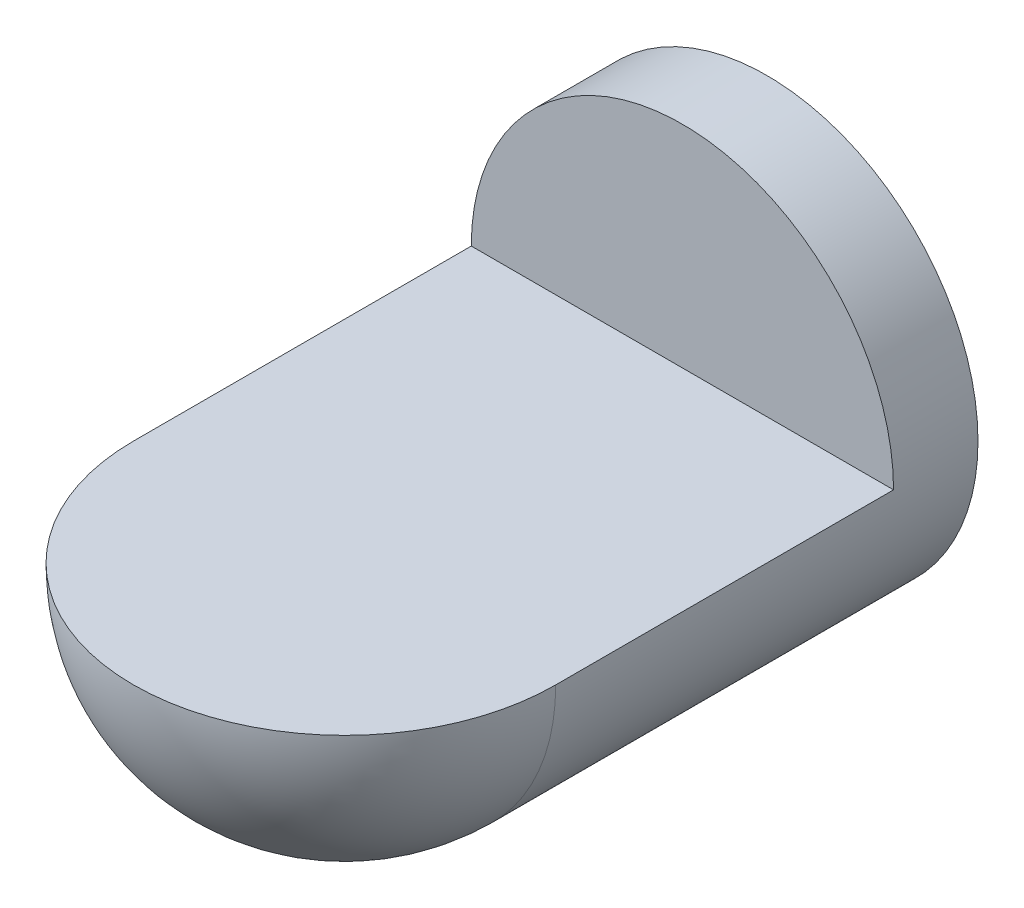
SolidWorks part; units mm, degrees
ref_plane "Front Plane" through (0, 0, 0) normal (0, 0, 1) x (1, 0, 0)
ref_plane "Top Plane" through (0, 0, 0) normal (0, 1, 0) x (1, 0, 0)
ref_plane "Right Plane" through (0, 0, 0) normal (1, 0, 0) x (0, 0, -1)
sketch "Sketch1" plane through (0, 0, 0) normal (1, 0, 0) x (0, 0, -1)
  line L0 (-146.9091, 0) -> (313.5945, 0) construction
  line L1 (150, 0) -> (-75, 0)
  line L2 (150, 0) -> (150, 75)
  line L3 (0, 75) -> (150, 75)
  arc A0 (-75, 0) -> (0, 75) centre (0, 0) cw
  dimension "D1" = 75
  dimension "D2" = 150
revolve "Revolve1" add sketch "Sketch1" angle 360 about L0
sketch "Sketch2" plane through (0, 0, 0) normal (1, 0, 0) x (0, 0, -1)
  line L0 (-88.0407, 0) -> (120.4455, 0) construction
  line L1 (120, 0) -> (120, 75)
  line L2 (150, 75) -> (0, 75) construction
  line L3 (120, 0) -> (-75, 0)
  line L4 (120, 75) -> (0, 75)
  line L5 (150, -75) -> (150, 75) construction
  arc A0 (0, 75) -> (0, -75) centre (0, 0) ccw construction
  arc A1 (-75, 0) -> (0, 75) centre (0, 0) cw
  dimension "D1" = 30
extrude "Cut-Extrude1" cut sketch "Sketch2" along normal through all and the other way through all
ref_axis "Axis1" through (0, 82.5, 0) along (0, -1, 0)
equation "\"link4_diameter\"=150"
equation "\"D1@Sketch1\"=\"link4_diameter\"/2"
equation "\"link4_length\"=150"
equation "\"D2@Sketch1\"=\"link4_length\""
equation "\"base_link_length\"=150"
equation "\"link1_diameter\"=150"
equation "\"link1_length\"=150"
equation "\"link2_diameter\"=150"
equation "\"link2_length\"=300"
equation "\"link3_diameter\"=150"
equation "\"link3_length\"=150"
equation "\"link5_diameter\"=150"
equation "\"link5_length\"=200"
equation "\"end_effector_diameter\"=150"
equation "\"end_effector_length\"=150"
equation "\"base_link_diameterA\"=200"
equation "\"base_link_diameterB\"=150"
equation "\"base_link_lengthA\"=50"
